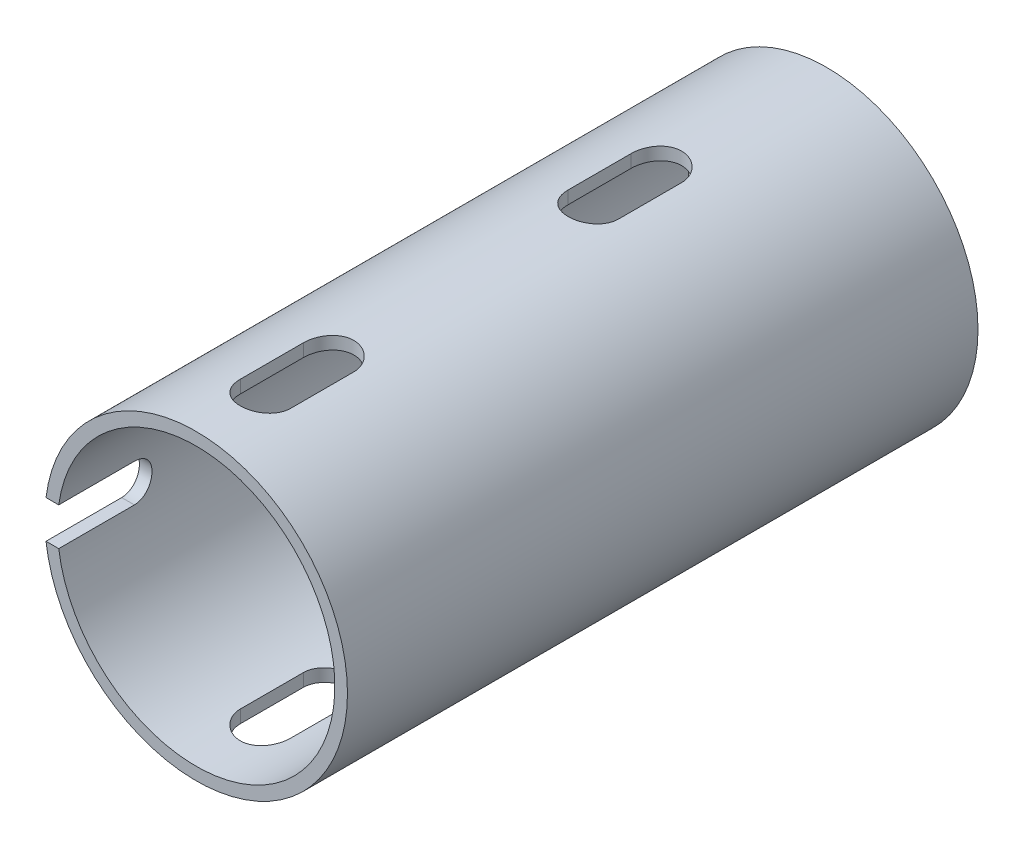
SolidWorks part; units mm, degrees
ref_plane "前视基准面" through (0, 0, 0) normal (0, 0, 1) x (1, 0, 0)
ref_plane "上视基准面" through (0, 0, 0) normal (0, 1, 0) x (1, 0, 0)
ref_plane "右视基准面" through (0, 0, 0) normal (1, 0, 0) x (0, 0, -1)
sketch "草图1" plane through (0, 0, 0) normal (0, 0, 1) x (1, 0, 0)
  circle A0 centre (0, 0) radius 22
  circle A1 centre (0, 0) radius 24
  dimension "D1" = 48
  dimension "D2" = 44
extrude "凸台-拉伸1" add sketch "草图1" along normal mid plane 100
ref_plane "基准面1" through (-24, 0, 0) normal (-1, 0, 0) x (0, 0, 1)
sketch "草图2" plane through (-24, 0, 0) normal (-1, 0, 0) x (0, 0, 1)
  line L0 (38, 3) -> (50, 3)
  line L1 (50, -24) -> (50, 24) construction
  line L2 (50, 3) -> (50, -3)
  line L3 (50, -3) -> (38, -3)
  arc A0 (38, 3) -> (38, -3) centre (38, 0) ccw
  point P1 (50, 0)
  dimension "D2" = 3
  dimension "D1" = 12
extrude "切除-拉伸1" cut sketch "草图2" against normal blind 20
ref_plane "基准面2" through (0, 24, 0) normal (0, 1, 0) x (1, 0, 0)
sketch "草图3" plane through (0, 24, 0) normal (0, 1, 0) x (1, 0, 0)
  line L0 (0, 13) -> (0, 23) construction
  line L1 (-4, 13) -> (-4, 23)
  line L2 (4, 13) -> (4, 23)
  line L3 (0, -39) -> (0, -29) construction
  line L4 (-4, -39) -> (-4, -29)
  line L5 (4, -39) -> (4, -29)
  line L6 (0, 9) -> (0, -25) construction
  arc A0 (-4, 13) -> (4, 13) centre (0, 13) ccw
  arc A1 (4, 23) -> (-4, 23) centre (0, 23) ccw
  arc A2 (-4, -39) -> (4, -39) centre (0, -39) ccw
  arc A3 (4, -29) -> (-4, -29) centre (0, -29) ccw
  point P3 (0, 18)
  point P8 (0, -34)
  point P15 (0, -22.6131)
  point P16 (0, -8)
  dimension "D3" = 4
  dimension "D1" = 10
  dimension "D2" = 10
  dimension "D4" = 52
  dimension "D5" = 8
extrude "切除-拉伸2" cut sketch "草图3" against normal through all
